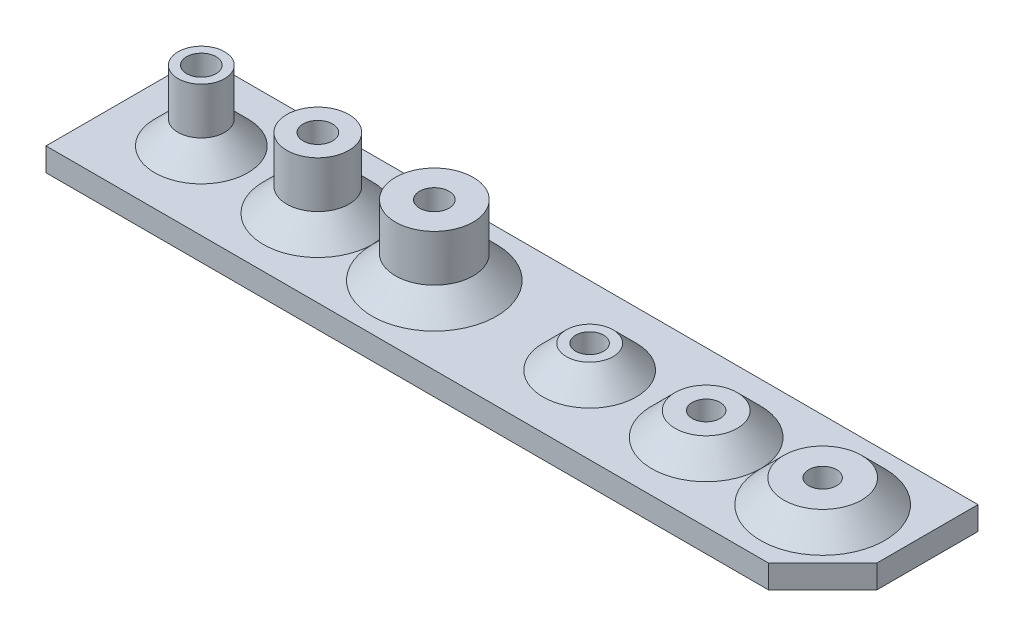
SolidWorks part; units mm, degrees
ref_plane "Front Plane" through (0, 0, 0) normal (0, 0, 1) x (1, 0, 0)
ref_plane "Top Plane" through (0, 0, 0) normal (0, 1, 0) x (1, 0, 0)
ref_plane "Right Plane" through (0, 0, 0) normal (1, 0, 0) x (0, 0, -1)
sketch "Sketch1" plane through (0, 0, 0) normal (0, 1, 0) x (1, 0, 0)
  line L1 (-50, -10) -> (50, -10)
  line L2 (-50, -10) -> (-50, 10)
  line L3 (-50, 10) -> (50, 10)
  line L4 (50, -10) -> (50, 10)
  line L5 (-50, -10) -> (50, 10) construction
  line L6 (-50, 10) -> (50, -10) construction
  point P0 (0, 0)
  dimension "D1" = 20
  dimension "D2" = 100
extrude "Boss-Extrude1" add sketch "Sketch1" along normal blind 3
sketch "Sketch2" plane through (0, 3, 0) normal (0, 1, 0) x (1, 0, 0)
  line L0 (-50, 10) -> (-50, -10) construction
  line L1 (50, 10) -> (-50, 10) construction
  circle A0 centre (-25, 0) radius 4
  circle A1 centre (-40, 0) radius 3
  circle A2 centre (-10, 0) radius 5
  point P10 (0, 0)
  point P11 (0, 0)
  point P12 (0, 0)
  point P13 (0, 0)
  dimension "D1" = 8
  dimension "D2" = 6
  dimension "D5" = 10
  dimension "D3" = 10
  dimension "D4" = 10
  dimension "D6" = 15
  dimension "D7" = 15
extrude "Boss-Extrude2" add sketch "Sketch2" along normal blind 9
chamfer "Chamfer1" distance 3 angle 45 1 edges at (-40, 3, -3)
hole_wizard "CSK for #6 Flat Head Machine Screw (100)1" positions "Sketch5" profile "Sketch7" countersink size "#6" standard "ANSI Inch" end condition through all
sketch "Sketch5" plane through (0, 0, 0) normal (0, -1, 0) x (-1, 0, 0)
  point P0 (40, 0)
sketch "Sketch7" plane through (-40, 0, 0) normal (1, 0, 0) x (0, 0, -1)
  line L0 (0, 0) -> (0, 12)
  line L1 (0, 12) -> (1.8986, 12)
  line L2 (1.8986, 12) -> (1.8986, 1.38)
  line L3 (1.8986, 1.38) -> (3.5433, 0)
  line L5 (3.5433, 0) -> (0, 0)
  line L6 (-1.8986, 1.38) -> (-3.5433, 0) construction
  line L11 (0, -6.35) -> (0, 107.95) construction
  dimension "Thru Hole Dia." = 3.7973
  dimension "Thru Hole Depth" = 12
  dimension "Near C'Sink Dia." = 7.0866
  dimension "Near C'Sink Angle" = 100
hole_wizard "CSK for #6 Flat Head Machine Screw (100)3" positions "Sketch10" profile "Sketch11" countersink size "#6" standard "ANSI Inch" end condition through all
sketch "Sketch10" plane through (0, 0, 0) normal (0, -1, 0) x (-1, 0, 0)
  point P0 (25, 0)
sketch "Sketch11" plane through (-25, 0, 0) normal (1, 0, 0) x (0, 0, -1)
  line L0 (0, 0) -> (0, 12)
  line L1 (0, 12) -> (1.8986, 12)
  line L2 (1.8986, 12) -> (1.8986, 1.38)
  line L3 (1.8986, 1.38) -> (3.5433, 0)
  line L5 (3.5433, 0) -> (0, 0)
  line L6 (-1.8986, 1.38) -> (-3.5433, 0) construction
  line L11 (0, -6.35) -> (0, 107.95) construction
  dimension "Thru Hole Dia." = 3.7973
  dimension "Thru Hole Depth" = 12
  dimension "Near C'Sink Dia." = 7.0866
  dimension "Near C'Sink Angle" = 100
hole_wizard "CSK for #6 Flat Head Machine Screw (100)4" positions "Sketch12" profile "Sketch13" countersink size "#6" standard "ANSI Inch" end condition through all
sketch "Sketch12" plane through (0, 0, 0) normal (0, -1, 0) x (-1, 0, 0)
  point P0 (10, 0)
sketch "Sketch13" plane through (-10, 0, 0) normal (1, 0, 0) x (0, 0, -1)
  line L0 (0, 0) -> (0, 12)
  line L1 (0, 12) -> (1.8986, 12)
  line L2 (1.8986, 12) -> (1.8986, 1.38)
  line L3 (1.8986, 1.38) -> (3.5433, 0)
  line L5 (3.5433, 0) -> (0, 0)
  line L6 (-1.8986, 1.38) -> (-3.5433, 0) construction
  line L11 (0, -6.35) -> (0, 107.95) construction
  dimension "Thru Hole Dia." = 3.7973
  dimension "Thru Hole Depth" = 12
  dimension "Near C'Sink Dia." = 7.0866
  dimension "Near C'Sink Angle" = 100
chamfer "Chamfer2" distance 3 angle 45 1 edges at (-25, 3, -4)
chamfer "Chamfer3" distance 3 angle 45 1 edges at (-10, 3, -5)
sketch "Sketch14" plane through (0, 3, 0) normal (0, 1, 0) x (1, 0, 0)
  line L0 (50, -10) -> (50, 10) construction
  circle A0 centre (10, 0) radius 3
  circle A1 centre (25, 0) radius 4
  circle A2 centre (40, 0) radius 5
  dimension "D1" = 6
  dimension "D2" = 8
  dimension "D3" = 10
  dimension "D4" = 10
  dimension "D5" = 15
  dimension "D6" = 15
extrude "Boss-Extrude3" add sketch "Sketch14" along normal blind 3
chamfer "Chamfer4" distance 3 angle 45 3 edges at (40, 3, -5) (25, 3, -4) (10, 3, -3)
hole_wizard "CBORE for M3 SBHCS1" positions "Sketch17" profile "Sketch18" counterbore size "M3" standard "ANSI Metric" end condition through all
sketch "Sketch17" plane through (0, 0, 0) normal (0, -1, 0) x (-1, 0, 0)
  point P0 (-10, 0)
sketch "Sketch18" plane through (10, 0, 0) normal (1, 0, 0) x (0, 0, -1)
  line L0 (0, 0) -> (0, 12)
  line L1 (0, 12) -> (1.8, 12)
  line L3 (1.8, 12) -> (1.8, 1.65)
  line L4 (3.35, 1.65) -> (1.8, 1.65)
  line L5 (3.35, 1.65) -> (3.35, 0.025)
  line L6 (3.35, 0.025) -> (3.375, 0)
  line L7 (3.375, 0) -> (0, 0)
  line L8 (-3.35, 0.025) -> (-3.375, 0) construction
  line L11 (0, -6.35) -> (0, 107.95) construction
  dimension "Thru Hole Dia." = 3.6
  dimension "Thru Hole Depth" = 12
  dimension "C'Bore Dia." = 6.7
  dimension "C'Bore Depth" = 1.65
  dimension "Near C'Sink Dia." = 6.75
  dimension "Near C'Sink Angle" = 90
pattern_linear "LPattern1" count 3 spacing 15 along (1, 0, 0) of "CBORE for M3 SBHCS1"
chamfer "Chamfer5" distance 7 angle 45 1 edges at (50, 1.5, 10)
